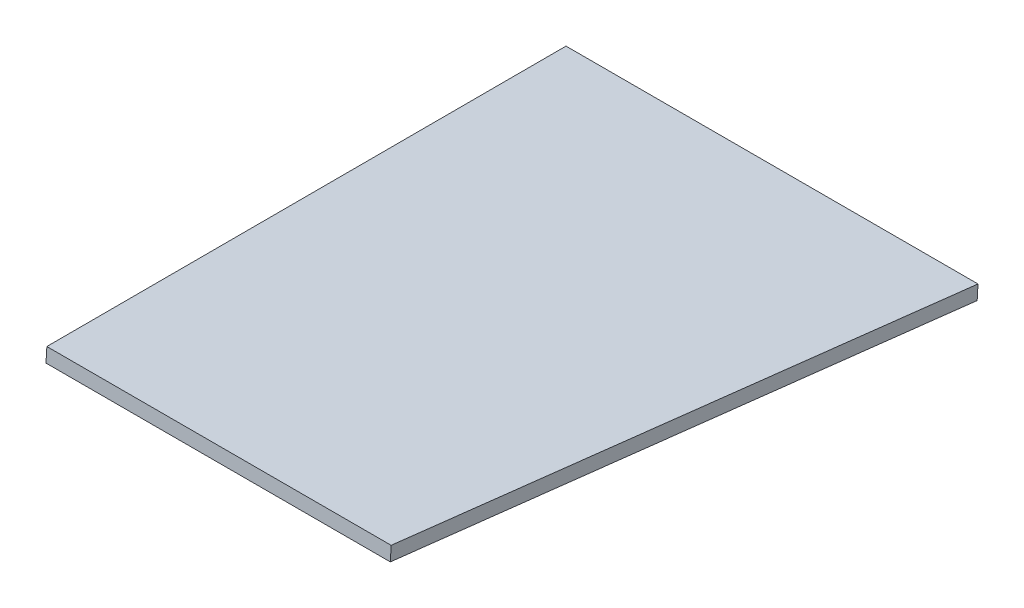
SolidWorks part; units mm, degrees
ref_plane "Front Plane" through (0, 0, 0) normal (0, 0, 1) x (1, 0, 0)
ref_plane "Top Plane" through (0, 0, 0) normal (0, 1, 0) x (1, 0, 0)
ref_plane "Right Plane" through (0, 0, 0) normal (1, 0, 0) x (0, 0, -1)
ref_plane "Pedlabox Floor Plane" through (0, -11.9121, 0.7164) normal (0, -0.9982, 0.06) x (-1, 0, 0)
sketch "PedalBox Floor" plane through (0, -11.9121, 0.7164) normal (0, -0.9982, 0.06) x (-1, 0, 0)
  line L0 (379.7615, -1353.0079) -> (410.4709, -1855.7502)
  line L1 (410.4709, -1855.7502) -> (722.929, -1855.7502)
  line L2 (722.929, -1855.7502) -> (753.6384, -1353.0079)
  line L3 (753.6384, -1353.0079) -> (379.7615, -1353.0079)
  line L5 (410.3712, -1854.1182) -> (379.2789, -1345.1062) construction
  line L6 (750.85, -1855.7502) -> (382.55, -1855.7502) construction
  line L7 (754.1211, -1345.1062) -> (723.0287, -1854.1182) construction
  line L8 (379.7615, -1353.0079) -> (753.6384, -1353.0079) construction
extrude "Boss-Extrude1" add sketch "PedalBox Floor" along normal blind 12.7 contours L3 L0 L1 L2
